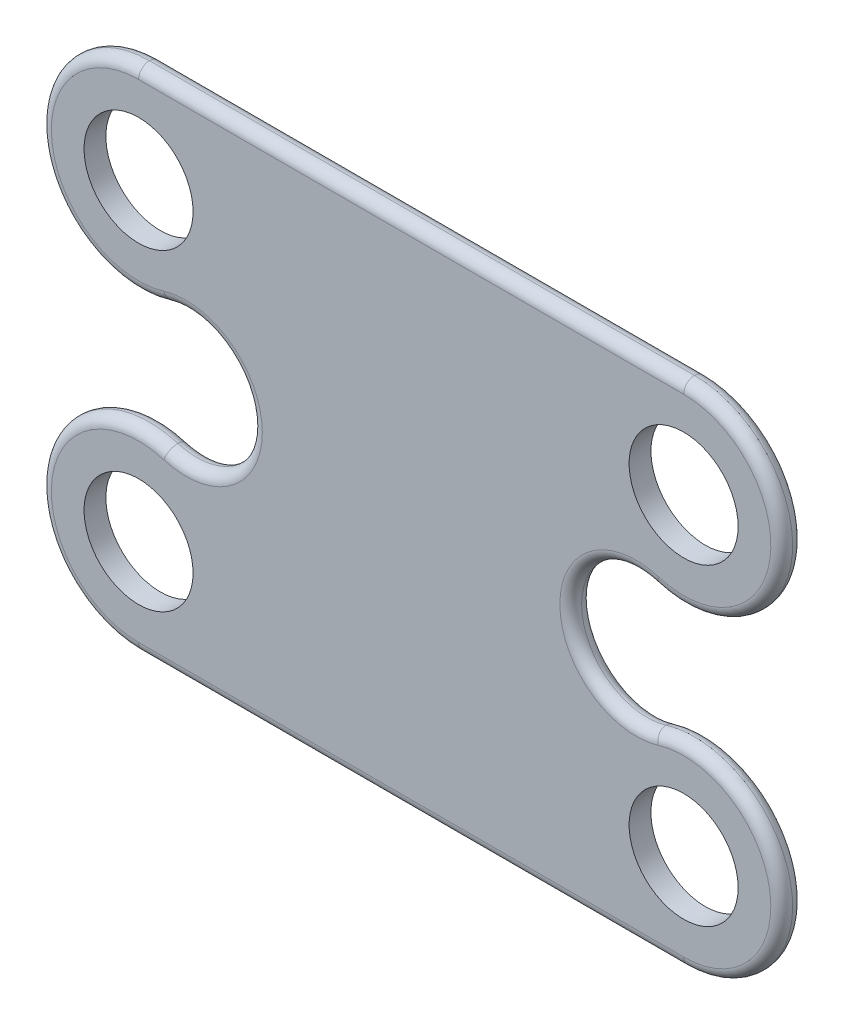
SolidWorks part; units mm, degrees
ref_plane "Płaszczyzna przednia" through (0, 0, 0) normal (0, 0, 1) x (1, 0, 0)
ref_plane "Płaszczyzna górna" through (0, 0, 0) normal (0, 1, 0) x (1, 0, 0)
ref_plane "Płaszczyzna prawa" through (0, 0, 0) normal (1, 0, 0) x (0, 0, -1)
sketch "Szkic2" plane through (0, 0, 0) normal (0, 0, 1) x (1, 0, 0)
  line L0 (0, 0) -> (76.7771, 0) construction
  line L1 (0, 0) -> (0, 49.2762) construction
  line L2 (-12.5, 0) -> (12.5, 0)
  line L3 (25, 23.3542) -> (-25, 23.3542)
  line L4 (25, -23.3542) -> (-25, -23.3542)
  arc A0 (22.3875, -5.7417) -> (22.3875, 5.7417) centre (20.6459, 0) cw
  arc A1 (22.3875, 5.7417) -> (25, 23.3542) centre (25, 14.3542) ccw
  circle A2 centre (25, 14.3542) radius 5
  arc A3 (-22.3875, -5.7417) -> (-22.3875, 5.7417) centre (-20.6459, 0) ccw
  circle A4 centre (-25, 14.3542) radius 5
  arc A5 (-22.3875, 5.7417) -> (-25, 23.3542) centre (-25, 14.3542) cw
  circle A6 centre (25, -14.3542) radius 5
  arc A7 (22.3875, -5.7417) -> (25, -23.3542) centre (25, -14.3542) cw
  circle A8 centre (-25, -14.3542) radius 5
  arc A9 (-22.3875, -5.7417) -> (-25, -23.3542) centre (-25, -14.3542) ccw
  point P10 (14.6459, 0)
  point P18 (0, 23.3542)
  dimension "D1" = 10
  dimension "D2" = 9
  dimension "D3" = 25
  dimension "D4" = 6
extrude "Dodanie-wyciągnięcie1" add sketch "Szkic2" along normal blind 2 contours A5 A3 L2 A0 A1 L3 A2 A4 | A3 A9 L4 A7 A0 L2 A6 A8 region at (33.0866, 13.1547, 0)
fillet "Zaokrąglenie1" radius 1 16 edges at (0, -23.3542, 2) (0, -23.3542, 0) (33.9026, -13.0336, 2) (33.9026, -13.0336, 0) (14.6459, 0, 2) (14.6459, 0, 0) (33.9026, 13.0336, 2) (33.9026, 13.0336, 0) (0, 23.3542, 2) (0, 23.3542, 0) (-33.9026, 13.0336, 2) (-33.9026, 13.0336, 0) (-33.9026, -13.0336, 2) (-33.9026, -13.0336, 0) (-14.6459, 0, 2) (-14.6459, 0, 0)
